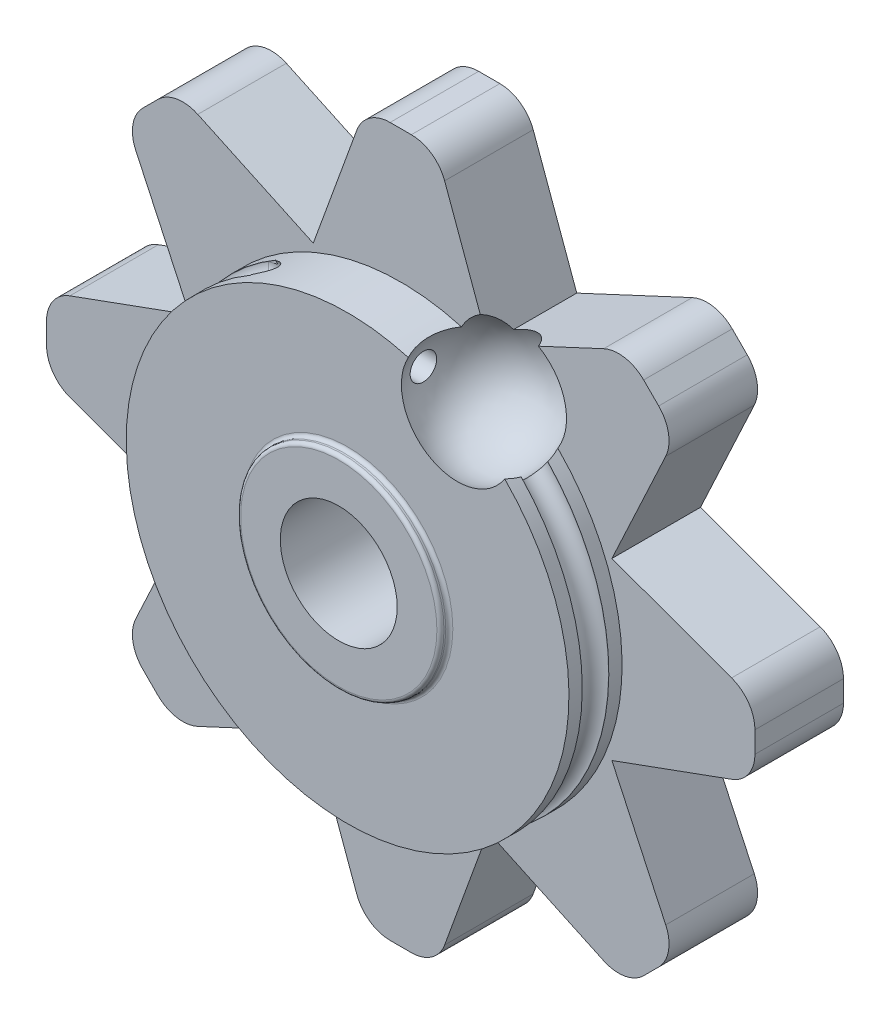
SolidWorks part; units mm, degrees
ref_plane "Front Plane" through (0, 0, 0) normal (0, 0, 1) x (1, 0, 0)
ref_plane "Top Plane" through (0, 0, 0) normal (0, 1, 0) x (1, 0, 0)
ref_plane "Right Plane" through (0, 0, 0) normal (1, 0, 0) x (0, 0, -1)
ref_axis "Axis1" through (-15.7375, 0, 0) along (1, 0, 0)
ref_axis "Axis2" through (0, 0, 2.1063) along (0, 0, -1)
ref_plane "Plane5" through (0, 0, 0) normal (0.866, 0.5, 0) x (0, 0, -1)
ref_plane "Plane6" through (3.1, 0, 0) normal (1, 0, 0) x (0, 0, -1)
sketch "Sketch1" plane through (0, 0, 0) normal (0, 0, 1) x (1, 0, 0)
  line L0 (-15.7375, 0) -> (15.7375, 0) construction
  circle A0 centre (0, 0) radius 6.25
  dimension "D1" = 12.5
extrude "body" add sketch "Sketch1" along normal blind 1.5 contours A0
sketch "Sketch2" plane through (0, 0, 0) normal (1, 0, 0) x (0, 0, -1)
  line L1 (0, 6.25) -> (-1.5, 6.25) construction
  line L2 (0, 5.25) -> (-1.5, 5.25) construction
  line L3 (-0.75, 5.25) -> (-0.75, -4.75) construction
  line L4 (0, -6.25) -> (0, 6.25) construction
  line L5 (0, -6.25) -> (0, 6.25) construction
  circle A0 centre (-0.75, 5.25) radius 0.375
  circle A1 centre (-0.75, -4.75) radius 0.375
  dimension "D1" = 0.75
  dimension "D3" = 0.75
  dimension "D4" = 1.5
  dimension "D2" = 1
extrude "Hole to trap cable knot" cut sketch "Sketch2" against normal through all and the other way blind 10 contours A0 | A1
ref_plane "Plane1" through (0, 0, 1.875) normal (0, 0, 1) x (1, 0, 0)
sketch "Sketch6" plane through (0, 0, 1.875) normal (0, 0, 1) x (1, 0, 0)
  line L0 (1.3991, -2.4232) -> (-1.3991, 2.4232) construction
  arc A0 (3.9111, 4.875) -> (2.7243, 5.625) centre (0, 0) ccw construction
  circle A2 centre (0, 0) radius 6.25 construction
  arc A3 (-3.125, 5.4127) -> (3.2608, 5.332) centre (0, 0) ccw
  arc A4 (3.9111, 4.875) -> (2.7243, 5.625) centre (0, 0) ccw construction
sketch "Sketch10" plane through (-5.4127, 9.375, 0) normal (-0.866, -0.5, 0) x (-0.5, 0.866, 0)
  line L0 (-4.5831, -1.125) -> (-3.8727, -1.125)
  line L1 (-3.8727, -1.125) -> (-3.8727, -0.3748)
  line L2 (-3.8727, -0.3748) -> (-4.5831, -0.3748)
  arc A0 (-4.5831, -0.3748) -> (-4.5831, -1.125) centre (-4.5831, -0.7499) ccw
  spline S0 degree 3 poles (-4.5903, -1.125) (-4.5759, -1.125) (-4.5739, -1.1025) (-4.5775, -1.0318) (-4.5799, -1.0018) (-4.5843, -0.9422) (-4.5859, -0.9199) (-4.589, -0.8665) (-4.5904, -0.8353) (-4.592, -0.7664) (-4.5919, -0.7281) (-4.5902, -0.6593) (-4.5887, -0.6289) (-4.5841, -0.5506) (-4.5809, -0.5129) (-4.5744, -0.422) (-4.574, -0.3902) (-4.5837, -0.3678) (-4.5938, -0.3778) (-4.6147, -0.4453) (-4.6227, -0.4771) (-4.6376, -0.5669) (-4.6447, -0.6281) (-4.6494, -0.7694) (-4.6461, -0.8461) (-4.6338, -0.9631) (-4.6257, -1.0065) (-4.603, -1.1026) (-4.5903, -1.125) (-4.5759, -1.125) (-4.5739, -1.1025) knots -0.125 -0.125 0 0 0.125 0.125 0.1875 0.1875 0.21875 0.21875 0.25 0.25 0.28125 0.28125 0.3125 0.3125 0.375 0.375 0.5 0.5 0.625 0.625 0.6875 0.6875 0.75 0.75 0.8125 0.8125 0.875 0.875 1 1 1.125 1.125 1.1875 only from (-4.5831, -1.125) to (-4.5831, -1.125) construction
  spline S1 degree 3 poles (-4.5903, -1.125) (-4.5759, -1.125) (-4.5739, -1.1025) (-4.5775, -1.0318) (-4.5799, -1.0018) (-4.5843, -0.9422) (-4.5859, -0.9199) (-4.589, -0.8665) (-4.5904, -0.8353) (-4.592, -0.7664) (-4.5919, -0.7281) (-4.5902, -0.6593) (-4.5887, -0.6289) (-4.5841, -0.5506) (-4.5809, -0.5129) (-4.5744, -0.422) (-4.574, -0.3902) (-4.5837, -0.3678) (-4.5938, -0.3778) (-4.6147, -0.4453) (-4.6227, -0.4771) (-4.6376, -0.5669) (-4.6447, -0.6281) (-4.6494, -0.7694) (-4.6461, -0.8461) (-4.6338, -0.9631) (-4.6257, -1.0065) (-4.603, -1.1026) (-4.5903, -1.125) (-4.5759, -1.125) (-4.5739, -1.1025) knots -0.125 -0.125 0 0 0.125 0.125 0.1875 0.1875 0.21875 0.21875 0.25 0.25 0.28125 0.28125 0.3125 0.3125 0.375 0.375 0.5 0.5 0.625 0.625 0.6875 0.6875 0.75 0.75 0.8125 0.8125 0.875 0.875 1 1 1.125 1.125 1.1875 only from (-4.5831, -1.125) to (-4.5831, -1.125) construction
  point P1 (-4.5831, -0.3748)
sweep "track for cable" cut profiles "Sketch10" path "Sketch6"
sketch "Sketch12" plane through (0, 0, 0) normal (0, 0, -1) x (-1, 0, 0)
  line L0 (0, 10) -> (0, -10) construction
  line L1 (-2.5653, 5.6993) -> (-1.2395, 9.342)
  line L2 (-0.2998, 10) -> (0.2998, 10)
  line L3 (1.2395, 9.342) -> (2.5653, 5.6993)
  line L6 (-3.2365, 3.8554) -> (3.2365, 3.8554) construction
  line L7 (-2.5653, 5.6993) -> (0, 0)
  line L8 (0, 0) -> (2.5653, 5.6993)
  arc A0 (-1.2395, 9.342) -> (-0.2998, 10) centre (-0.2998, 9) cw
  arc A1 (0.2998, 10) -> (1.2395, 9.342) centre (0.2998, 9) cw
  circle A4 centre (0, 0) radius 6.25 construction
  point P9 (-1, 10)
  point P12 (1, 10)
  dimension "D6" = 1
  dimension "D1" = 20
  dimension "D2" = 2
  dimension "D3" = 6.4729
  dimension "D4" = 110
  dimension "D5" = 110
sketch "Sketch14" plane through (0, 0, 0) normal (0, 0, -1) x (-1, 0, 0)
  line L0 (5.7294, 7.4823) -> (2.4696, 5.9622)
  line L1 (7.2831, 6.8591) -> (6.8591, 7.2831)
  line L2 (5.9622, 2.4696) -> (7.4823, 5.7294)
  line L3 (0, 0) -> (5.844, 2.216) construction
  line L4 (2.216, 5.844) -> (0, 0) construction
  line L5 (-1.2395, 9.342) -> (-2.5653, 5.6993)
  line L6 (0.2998, 10) -> (-0.2998, 10)
  line L7 (2.5653, 5.6993) -> (1.2395, 9.342)
  line L8 (0, 0) -> (2.5653, 5.6993)
  line L9 (0, 0) -> (2.5653, 5.6993) construction
  line L10 (-1.2395, 9.342) -> (-2.4696, 5.9622)
  line L11 (0.2998, 10) -> (-0.2998, 10)
  line L12 (2.4696, 5.9622) -> (1.2395, 9.342)
  line L13 (-2.5653, 5.6993) -> (0, 0)
  line L14 (-2.5653, 5.6993) -> (0, 0) construction
  line L15 (9.342, 1.2395) -> (5.9622, 2.4696)
  line L16 (10, -0.2998) -> (10, 0.2998)
  line L17 (5.9622, -2.4696) -> (9.342, -1.2395)
  line L18 (0, 0) -> (5.6993, -2.5653) construction
  line L19 (5.6993, 2.5653) -> (0, 0) construction
  line L20 (7.4823, -5.7294) -> (5.9622, -2.4696)
  line L21 (6.8591, -7.2831) -> (7.2831, -6.8591)
  line L22 (2.4696, -5.9622) -> (5.7294, -7.4823)
  line L23 (0, 0) -> (2.216, -5.844) construction
  line L24 (5.844, -2.216) -> (0, 0) construction
  line L25 (1.2395, -9.342) -> (2.4696, -5.9622)
  line L26 (-0.2998, -10) -> (0.2998, -10)
  line L27 (-2.4696, -5.9622) -> (-1.2395, -9.342)
  line L28 (0, 0) -> (-2.5653, -5.6993) construction
  line L29 (2.5653, -5.6993) -> (0, 0) construction
  line L30 (-5.7294, -7.4823) -> (-2.4696, -5.9622)
  line L31 (-7.2831, -6.8591) -> (-6.8591, -7.2831)
  line L32 (-5.9622, -2.4696) -> (-7.4823, -5.7294)
  line L33 (0, 0) -> (-5.844, -2.216) construction
  line L34 (-2.216, -5.844) -> (0, 0) construction
  line L35 (-9.342, -1.2395) -> (-5.9622, -2.4696)
  line L36 (-10, 0.2998) -> (-10, -0.2998)
  line L37 (-5.9622, 2.4696) -> (-9.342, 1.2395)
  line L38 (0, 0) -> (-5.6993, 2.5653) construction
  line L39 (-5.6993, -2.5653) -> (0, 0) construction
  line L40 (-7.4823, 5.7294) -> (-5.9622, 2.4696)
  line L41 (-6.8591, 7.2831) -> (-7.2831, 6.8591)
  line L42 (-2.4696, 5.9622) -> (-5.7294, 7.4823)
  line L43 (0, 0) -> (-2.216, 5.844) construction
  line L44 (-5.844, 2.216) -> (0, 0) construction
  arc A0 (6.8591, 7.2831) -> (5.7294, 7.4823) centre (6.152, 6.5759) ccw
  arc A1 (7.4823, 5.7294) -> (7.2831, 6.8591) centre (6.5759, 6.152) ccw
  arc A2 (-0.2998, 10) -> (-1.2395, 9.342) centre (-0.2998, 9) ccw
  arc A3 (1.2395, 9.342) -> (0.2998, 10) centre (0.2998, 9) ccw
  arc A4 (-0.2998, 10) -> (-1.2395, 9.342) centre (-0.2998, 9) ccw
  arc A5 (1.2395, 9.342) -> (0.2998, 10) centre (0.2998, 9) ccw
  arc A6 (10, 0.2998) -> (9.342, 1.2395) centre (9, 0.2998) ccw
  arc A7 (9.342, -1.2395) -> (10, -0.2998) centre (9, -0.2998) ccw
  arc A8 (7.2831, -6.8591) -> (7.4823, -5.7294) centre (6.5759, -6.152) ccw
  arc A9 (5.7294, -7.4823) -> (6.8591, -7.2831) centre (6.152, -6.5759) ccw
  arc A10 (0.2998, -10) -> (1.2395, -9.342) centre (0.2998, -9) ccw
  arc A11 (-1.2395, -9.342) -> (-0.2998, -10) centre (-0.2998, -9) ccw
  arc A12 (-6.8591, -7.2831) -> (-5.7294, -7.4823) centre (-6.152, -6.5759) ccw
  arc A13 (-7.4823, -5.7294) -> (-7.2831, -6.8591) centre (-6.5759, -6.152) ccw
  arc A14 (-10, -0.2998) -> (-9.342, -1.2395) centre (-9, -0.2998) ccw
  arc A15 (-9.342, 1.2395) -> (-10, 0.2998) centre (-9, 0.2998) ccw
  arc A16 (-7.2831, 6.8591) -> (-7.4823, 5.7294) centre (-6.5759, 6.152) ccw
  arc A17 (-5.7294, 7.4823) -> (-6.8591, 7.2831) centre (-6.152, 6.5759) ccw
  point P67 (0, 0)
  dimension "D1" = 0
  dimension "D2" = 8
extrude "thumb grip" add sketch "Sketch14" along normal blind 2.5
sketch "Sketch13" plane through (0, 0, 1.5) normal (0, 0, 1) x (1, 0, 0)
  circle A0 centre (0, 0) radius 1.65
  dimension "D1" = 3.3
extrude "hole for screw" cut sketch "Sketch13" against normal through all
sketch "Sketch20" plane through (3.1, 0, 0) normal (1, 0, 0) x (0, 0, -1)
  line L0 (-0.75, 7) -> (-0.75, 3.5)
  line L1 (-0.75, 7.7934) -> (-0.75, 1.6513) construction
  circle A0 centre (-0.75, 5.25) radius 1.75 construction
  arc A1 (-0.3841, 5.332) -> (-1.1159, 5.332) centre (-0.75, 5.25) ccw construction
  arc A2 (-0.3841, 5.332) -> (-1.1159, 5.332) centre (-0.75, 5.25) ccw construction
  arc A3 (-0.75, 7) -> (-0.75, 3.5) centre (-0.75, 5.25) cw
  dimension "D1" = 3.5
revolve "trap for ball" cut sketch "Sketch20" angle 360 about L1
sketch "Sketch21" plane through (0, 0, 1.5) normal (0, 0, 1) x (1, 0, 0)
  circle A0 centre (0, 0) radius 2.8716
  circle A3 centre (0, 0) radius 1.65 construction
  circle A4 centre (0, 0) radius 1.65
extrude "lip to contact handle" add sketch "Sketch21" along normal blind 0.25 and the other way blind 4.25
fillet "Fillet1" radius 0.1 4 edges at (2.8716, 0, 1.5) (2.8716, 0, 1.75) (-2.8716, 0, -2.5) (2.8716, 0, -2.75)
equation "\"Do\"=7.5mm"
equation "\"Lo\"=10"
equation "\"screw_diam\"= 3.5mm"
equation "\"wheel_Do\"=12.5mm"
equation "\"wheel_thickness\"=4mm"
equation "\"Collet_diameter\"=4.3"
equation "\"clearance\"= 0.5mm"
equation "\"D1@Sketch1\"=\"wheel_Do\""
equation "\"wheel_total_diam_ent\"=20"
equation "\"D1@Sketch12\"=\"wheel_total_diam_ent\""
equation "\"handle_body_width\"= 10mm"
equation "\"finger_diameter\"=35"
equation "\"collet_lid_diameter\"=10"
equation "\"screw_cap_diam\"=5.15"
equation "\"handle_thickness\"=12.5mm"
equation "\"post_hole_diam\"=2"
equation "\"roll_rod_diam\"= 6.5 "
equation "\"roll_rod_length\"=6.6"
equation "\"disc_diam\"=5"
equation "\"disc_width\"=1.5"
equation "\"arm_width\"=5"
equation "\"arm_thickness\"=4.5"
equation "\"wheel_total_diam\"=30"
equation "\"D1@thumb grip\"=\"wheel_thickness\"-1.5"
equation "\"D1@body\"=\"wheel_thickness\""
